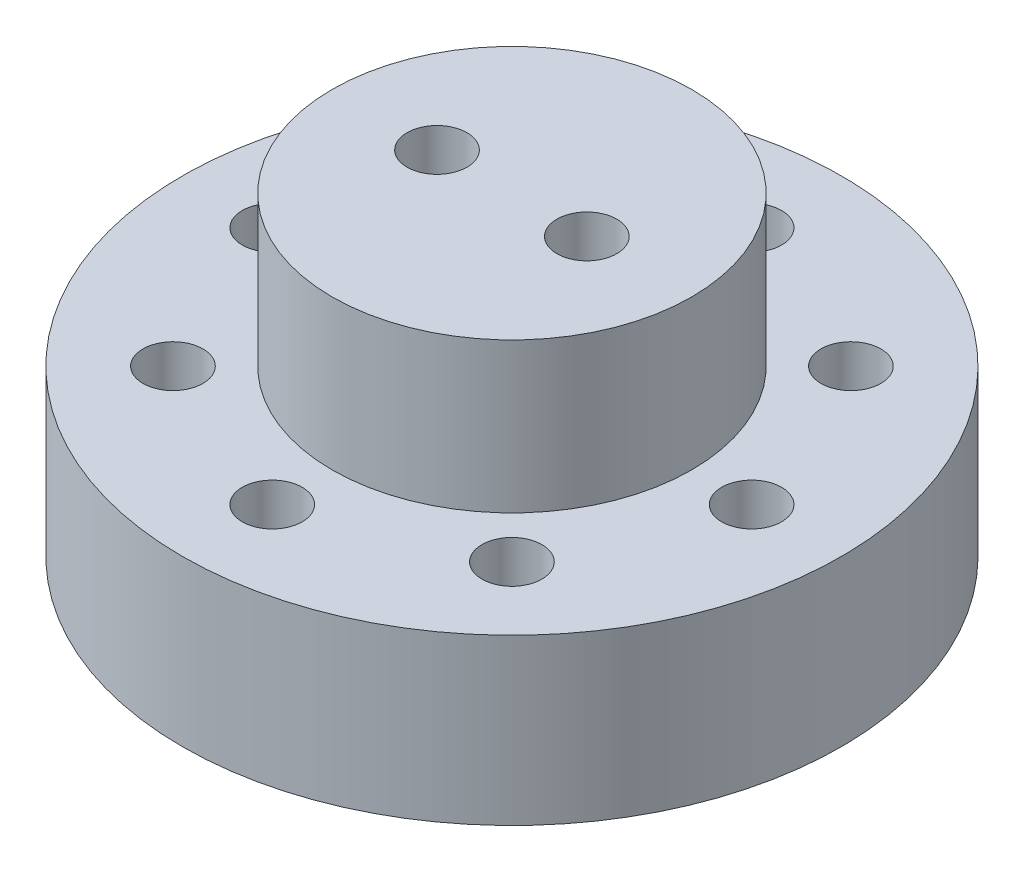
SolidWorks part; units mm, degrees
material "1060 Alloy"
ref_plane "Front Plane" through (0, 0, 0) normal (0, 0, 1) x (1, 0, 0)
ref_plane "Top Plane" through (0, 0, 0) normal (0, 1, 0) x (1, 0, 0)
ref_plane "Right Plane" through (0, 0, 0) normal (1, 0, 0) x (0, 0, -1)
sketch "Sketch1" plane through (0, 0, 0) normal (0, 1, 0) x (1, 0, 0)
  circle A0 centre (0, 0) radius 11
  circle A1 centre (0, 8) radius 1
  circle A2 centre (5.6569, 5.6569) radius 1
  circle A3 centre (8, 0) radius 1
  circle A4 centre (5.6569, -5.6569) radius 1
  circle A5 centre (0, -8) radius 1
  circle A6 centre (-5.6569, -5.6569) radius 1
  circle A7 centre (-8, 0) radius 1
  circle A8 centre (-5.6569, 5.6569) radius 1
  point P22 (0, 0)
  dimension "D1" = 22
  dimension "D2" = 2
  dimension "D6" = 8
  dimension "D3" = 8
  dimension "D5" = 8
  dimension "D4" = 8
extrude "Boss-Extrude1" add sketch "Sketch1" along normal blind 5.5
sketch "Sketch2" plane through (0, 5.5, 0) normal (0, 1, 0) x (1, 0, 0)
  circle A0 centre (0, 0) radius 4
  dimension "D1" = 8
extrude "Cut-Extrude1" cut sketch "Sketch2" against normal through all
ref_plane "Plane1" through (0, 3.5, 0) normal (0, 1, 0) x (1, 0, 0)
sketch "Sketch3" plane through (0, 3.5, 0) normal (0, 1, 0) x (1, 0, 0)
  circle A0 centre (0, 0) radius 5
  circle A1 centre (0, 0) radius 11
  dimension "D1" = 10
  dimension "D2" = 22
sketch "Sketch4" plane through (0, 5.5, 0) normal (0, 1, 0) x (1, 0, 0)
  line L1 (-0.75, 12.5) -> (0.75, 12.5)
  line L2 (-0.75, 12.5) -> (-0.75, 9.5)
  line L3 (-0.75, 9.5) -> (0.75, 9.5)
  line L4 (0.75, 12.5) -> (0.75, 9.5)
  line L5 (-0.75, 12.5) -> (0.75, 9.5) construction
  line L6 (-0.75, 9.5) -> (0.75, 12.5) construction
  circle A0 centre (0, 0) radius 11 construction
  point P0 (0, 11)
  dimension "D1" = 1.5
  dimension "D2" = 3
extrude "Cut-Extrude3" [suppressed] cut sketch "Sketch4" against normal blind 4
sketch "Sketch5" plane through (0, 5.5, 0) normal (0, 1, 0) x (1, 0, 0)
  circle A0 centre (0, 0) radius 4
  circle A1 centre (0, 0) radius 6
  dimension "D1" = 8
  dimension "D2" = 12
extrude "Boss-Extrude2" [suppressed] add sketch "Sketch5" along normal blind 20 contours A1 | A0
sketch "Sketch6" [suppressed] plane through (0, 22, 0) normal (0, 1, 0) x (1, 0, 0)
  line L0 (-0.255, 0.9669) -> (0.255, 0.9669)
  line L1 (-0.255, 0.9669) -> (-0.255, 1.4769)
  line L2 (0.255, 0.9669) -> (0.255, 1.4769)
  line L3 (-0.255, 1.4769) -> (0.255, 1.4769)
  line L4 (-0.254, -0.9672) -> (0.254, -0.9672)
  line L5 (-0.254, -0.9672) -> (-0.254, -1.4752)
  line L6 (0.254, -0.9672) -> (0.254, -1.4752)
  line L7 (-0.254, -1.4752) -> (0.254, -1.4752)
  line L8 (0.9672, 0.254) -> (0.9672, -0.254)
  line L9 (0.9672, 0.254) -> (1.4752, 0.254)
  line L10 (0.9672, -0.254) -> (1.4752, -0.254)
  line L11 (1.4752, 0.254) -> (1.4752, -0.254)
  line L12 (-0.9672, 0.254) -> (-0.9672, -0.254)
  line L13 (-0.9672, 0.254) -> (-1.4752, 0.254)
  line L14 (-0.9672, -0.254) -> (-1.4752, -0.254)
  line L15 (-1.4752, 0.254) -> (-1.4752, -0.254)
  circle A0 centre (0, 0) radius 1
  circle A1 centre (0, 0) radius 4
  circle A2 centre (0, 0) radius 6
  circle M4 centre (0, 0) radius 6
  circle M5 centre (0, 0) radius 4
  dimension "D1" = 2
  dimension "D4" = 8
  dimension "D5" = 12
  dimension "D2" = 0.51
  dimension "D3" = 0.51
  dimension "D6" = 0.508
  dimension "D7" = 0.508
  dimension "D8" = 0.508
  dimension "D9" = 0.508
  dimension "D10" = 0.508
  dimension "D11" = 0.508
extrude "Boss-Extrude3" [suppressed] add sketch "Sketch6" along normal blind 20 contours A0 L1 L3 L2 M5 | M4 M5
sketch "Sketch7" plane through (0, 0, 0) normal (0, 0, 1) x (1, 0, 0)
  line L0 (11, 3.5) -> (-11, 3.5) construction
  circle A0 centre (0, 38.5) radius 1
  dimension "D1" = 2
  dimension "D2" = 35
extrude "Cut-Extrude4" [suppressed] cut sketch "Sketch7" against normal blind 1 and the other way blind 5
sketch "Sketch9" plane through (0, 5.5, 0) normal (0, 1, 0) x (1, 0, 0)
  circle A0 centre (0, 0) radius 6
  dimension "D1" = 12
extrude "Boss-Extrude4" add sketch "Sketch9" along normal blind 5
sketch "Sketch10" plane through (0, 10.5, 0) normal (0, 1, 0) x (1, 0, 0)
  line L0 (-2.5, 0) -> (2.5, 0) construction
  circle A0 centre (-2.5, 0) radius 1
  circle A1 centre (2.5, 0) radius 1
  point P4 (0, 0)
  dimension "D2" = 2
  dimension "D3" = 2
  dimension "D1" = 5
extrude "Cut-Extrude6" cut sketch "Sketch10" against normal through all
ref_plane "Plane2" through (0, 0, 6) normal (0, 0, 1) x (1, 0, 0)
sketch "Sketch8" [suppressed] plane through (0, 0, 6) normal (0, 0, 1) x (1, 0, 0)
  circle A0 centre (0, 35) radius 2
  dimension "D1" = 4
extrude "Cut-Extrude5" [suppressed] cut sketch "Sketch8" against normal blind 1
